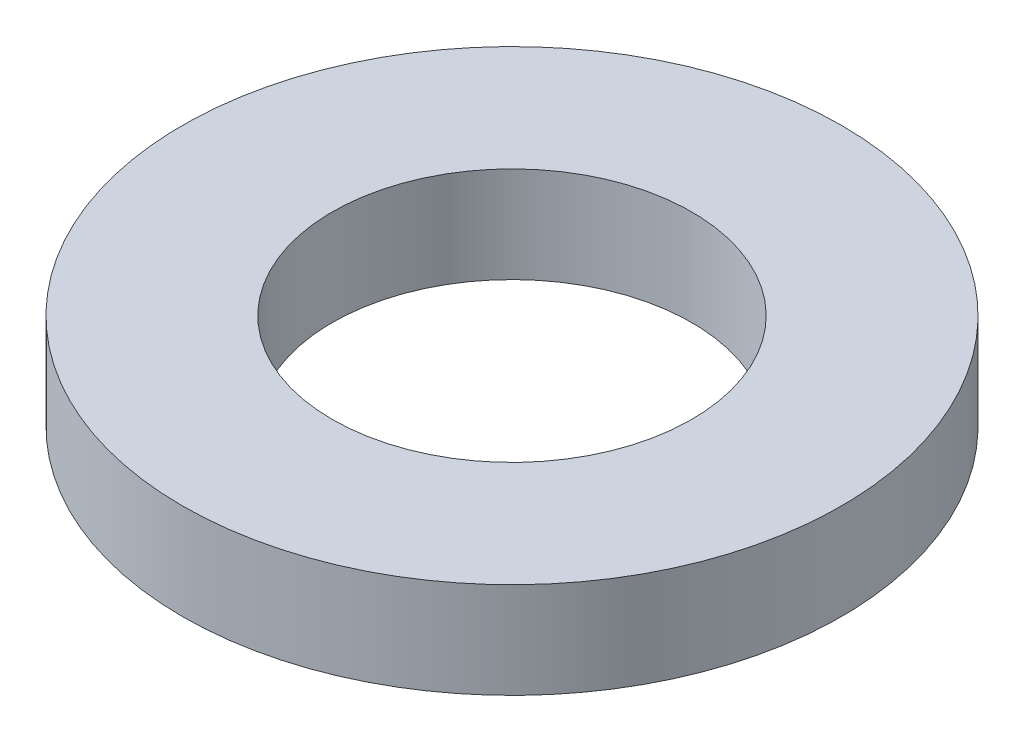
SolidWorks part; units mm, degrees
ref_plane "Front Plane" through (0, 0, 0) normal (0, 0, 1) x (1, 0, 0)
ref_plane "Top Plane" through (0, 0, 0) normal (0, 1, 0) x (1, 0, 0)
ref_plane "Right Plane" through (0, 0, 0) normal (1, 0, 0) x (0, 0, -1)
sketch "Sketch1" plane through (0, 0, 0) normal (0, 1, 0) x (1, 0, 0)
  circle A0 centre (0, 0) radius 82.5
  dimension "FLANGE_OD" = 165
extrude "Boss-Extrude1" add sketch "Sketch1" along normal blind 24
sketch "Sketch2" plane through (0, 0, 0) normal (0, 1, 0) x (1, 0, 0)
  circle A0 centre (0, 0) radius 45
  dimension "BORE_D" = 90
extrude "Cut-Extrude1" cut sketch "Sketch2" along normal through all
sketch "Sketch3" plane through (0, 24, 0) normal (0, 1, 0) x (1, 0, 0)
  circle A0 centre (0, 0) radius 31.1633 construction
  circle A1 centre (-31.1633, 0) radius 3.6172
  dimension "BOLT_D" = 7.2344
  dimension "BOLT_PCD" = 62.3267
extrude "Cut-Extrude2" cut sketch "Sketch3" against normal blind 23.9085 rebuild error yes
pattern_circular "CirPattern1" count 3 over 360 rebuild error yes
